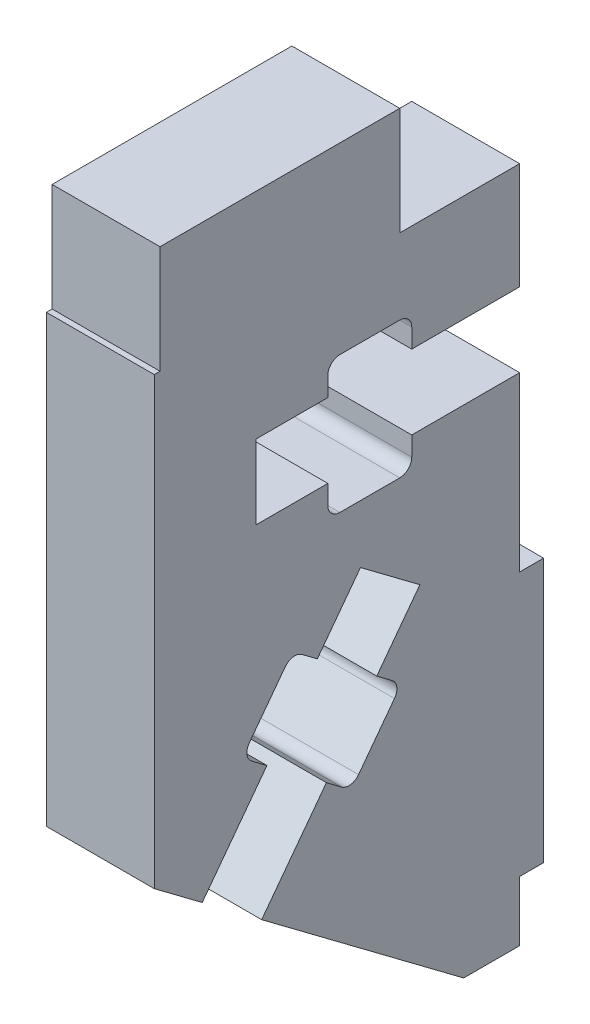
SolidWorks part; units mm, degrees
ref_plane "Front Plane" through (0, 0, 0) normal (0, 0, 1) x (1, 0, 0)
ref_plane "Top Plane" through (0, 0, 0) normal (0, 1, 0) x (1, 0, 0)
ref_plane "Right Plane" through (0, 0, 0) normal (1, 0, 0) x (0, 0, -1)
sketch "Sketch1" plane through (0, 0, 0) normal (1, 0, 0) x (0, 0, -1)
  line L0 (0, 0) -> (0, -30)
  line L1 (0, -30) -> (-40, 0)
  line L2 (-40, 0) -> (0, 0)
  dimension "D1" = 40
  dimension "D2" = 30
extrude "Boss-Extrude1" add sketch "Sketch1" along normal blind 4.5
sketch "Sketch2" plane through (4.5, 0, 0) normal (1, 0, 0) x (0, 0, -1)
  line L0 (0, -25.75) -> (1, -25.75)
  line L1 (0, -30) -> (0, 0) construction
  line L2 (1, -25.75) -> (1, -14.75)
  line L3 (1, -14.75) -> (0, -14.75)
  line L4 (0, -14.75) -> (0, -25.75)
  line L5 (1, -20.25) -> (0, -20.25) construction
  line L6 (0, -14.75) -> (4.5, -14.75) construction
  line L7 (0, -25.75) -> (4.5, -25.75) construction
  dimension "D1" = 0
  dimension "D2" = 1
  dimension "D3" = 0
extrude "Boss-Extrude2" add sketch "Sketch2" against normal through all
sketch "Sketch3" plane through (4.5, 0, 0) normal (1, 0, 0) x (0, 0, -1)
  line L0 (0, -6) -> (-11, -6) construction
  line L1 (0, -14.75) -> (0, 0) construction
  line L2 (-11, -7.55) -> (-11, -4.45) construction
  line L3 (-11, -4.45) -> (0, -4.45) construction
  line L4 (0, -4.45) -> (-4.5, -4.45)
  line L5 (-4.5, -4.45) -> (-4.5, -3.65)
  line L6 (-5, -3.15) -> (-7.5, -3.15)
  line L7 (-8, -3.65) -> (-8, -4.45)
  line L8 (-8, -4.45) -> (-11, -4.45)
  line L9 (-11, -4.45) -> (-11, -7.55)
  line L10 (0, -4.45) -> (0, -7.55)
  line L12 (-11, -7.55) -> (0, -7.55) construction
  line L13 (-8, -7.55) -> (-11, -7.55)
  line L14 (-8, -8.35) -> (-8, -7.55)
  line L15 (-5, -8.85) -> (-7.5, -8.85)
  line L16 (-4.5, -7.55) -> (-4.5, -8.35)
  line L17 (0, -7.55) -> (-4.5, -7.55)
  arc A0 (-4.5, -3.65) -> (-5, -3.15) centre (-5, -3.65) ccw
  arc A1 (-7.5, -3.15) -> (-8, -3.65) centre (-7.5, -3.65) ccw
  arc A2 (-7.5, -8.85) -> (-8, -8.35) centre (-7.5, -8.35) cw
  arc A3 (-4.5, -8.35) -> (-5, -8.85) centre (-5, -8.35) cw
  point P15 (-4.5, -3.15)
  point P18 (-8, -3.15)
  point P29 (-8, -8.85)
  point P30 (-4.5, -8.85)
  dimension "D7" = 0.5
  dimension "D1" = 11
  dimension "D2" = 1.55
  dimension "D3" = 3.5
  dimension "D4" = 2.85
  dimension "D5" = 8
  dimension "D6" = 6
extrude "Cut-Extrude1" cut sketch "Sketch3" against normal through all
sketch "Sketch4" plane through (4.5, 0, 0) normal (1, 0, 0) x (0, 0, -1)
  line L0 (-13.24, -20.07) -> (-6.64, -11.27) construction
  line L1 (-40, 0) -> (0, -30) construction
  line L2 (-6.64, -11.27) -> (-4.16, -13.13) construction
  line L3 (-5.4, -12.2) -> (-12, -21) construction
  line L4 (-10.76, -21.93) -> (-13.24, -20.07)
  line L5 (-13.24, -20.07) -> (-10.54, -16.47)
  line L6 (-10.54, -16.47) -> (-11.18, -15.99)
  line L7 (-11.28, -15.29) -> (-9.78, -13.29)
  line L8 (-9.08, -13.19) -> (-8.44, -13.67)
  line L9 (-8.44, -13.67) -> (-6.64, -11.27)
  line L10 (-6.64, -11.27) -> (-4.16, -13.13)
  line L11 (0, 0) -> (-40, 0) construction
  line L12 (-10.76, -21.93) -> (-4.16, -13.13) construction
  line L13 (-5.96, -15.53) -> (-4.16, -13.13)
  line L14 (-5.32, -16.01) -> (-5.96, -15.53)
  line L15 (-6.72, -18.71) -> (-5.22, -16.71)
  line L16 (-8.06, -18.33) -> (-7.42, -18.81)
  line L17 (-10.76, -21.93) -> (-8.06, -18.33)
  arc A0 (-11.18, -15.99) -> (-11.28, -15.29) centre (-10.88, -15.59) cw
  arc A1 (-9.78, -13.29) -> (-9.08, -13.19) centre (-9.38, -13.59) cw
  arc A2 (-5.22, -16.71) -> (-5.32, -16.01) centre (-5.62, -16.41) ccw
  arc A3 (-7.42, -18.81) -> (-6.72, -18.71) centre (-7.12, -18.41) ccw
  point P14 (-11.58, -15.69)
  point P17 (-9.48, -12.89)
  point P28 (-4.92, -16.31)
  point P29 (-7.02, -19.11)
  dimension "D7" = 0.5
  dimension "D1" = 11
  dimension "D2" = 1.55
  dimension "D3" = 3.5
  dimension "D4" = 2.85
  dimension "D5" = 8
  dimension "D6" = 21
extrude "Cut-Extrude2" cut sketch "Sketch4" against normal through all
sketch "Sketch5" plane through (4.5, 0, 0) normal (1, 0, 0) x (0, 0, -1)
  line L0 (-15.24, -18.57) -> (-15.24, 0)
  line L1 (-40, 0) -> (-13.24, -20.07) construction
  line L2 (0, 0) -> (-40, 0) construction
  line L3 (-15.24, 0) -> (-40, 0)
  line L4 (-40, 0) -> (-15.24, -18.57)
  dimension "D1" = 2
extrude "Cut-Extrude3" cut sketch "Sketch5" against normal through all
sketch "Sketch6" plane through (0, 0, 11) normal (0, 0, -1) x (-1, 0, 0)
  line L0 (-2.25, -4.45) -> (-2.25, -7.55) construction
  line L1 (0, -4.45) -> (-4.5, -4.45) construction
  line L2 (0, -7.55) -> (-4.5, -7.55) construction
  circle A0 centre (-2.25, -6) radius 1.5
  dimension "D1" = 3
sketch "Sketch7" plane through (0, -10.4, 7.8) normal (0, -0.8, 0.6) x (1, 0, 0)
  line L0 (2.25, -1.45) -> (2.25, -4.55) construction
  line L1 (0, -1.45) -> (4.5, -1.45) construction
  line L2 (0, -4.55) -> (4.5, -4.55) construction
  circle A0 centre (2.25, -3) radius 1.55
sketch "Sketch8" plane through (4.5, 0, 0) normal (1, 0, 0) x (0, 0, -1)
  line L0 (-10, 4.5) -> (-10, 0) construction
  line L1 (-15, 0) -> (-5, 0)
  line L2 (-15, 0) -> (-15, 4.5)
  line L3 (-15, 4.5) -> (-5, 4.5)
  line L4 (-5, 0) -> (-5, 4.5)
  line L5 (0, 0) -> (-15.24, 0) construction
  dimension "D1" = 10
  dimension "D2" = 4.5
  dimension "D3" = 10
extrude "Boss-Extrude3" add sketch "Sketch8" against normal through all
sketch "Sketch10" plane through (4.5, 0, 0) normal (1, 0, 0) x (0, 0, -1)
  line L0 (0, -28.25) -> (-2.3333, -28.25)
  line L1 (0, -30) -> (0, -25.75) construction
  line L2 (-10.76, -21.93) -> (0, -30) construction
  line L3 (-2.3333, -28.25) -> (0, -30)
  line L4 (0, -30) -> (0, -28.25)
  dimension "D1" = 0
extrude "Cut-Extrude4" cut sketch "Sketch10" against normal through all contours L0 L3 L4
equation "\"X-ROD-SPACING\"=45"
equation "\"Y-ROD-SPACING\"=75"
equation "\"Z-ROD-SPACING\"=17.5"
equation "\"Y-BED-OFFSET\"=2"
equation "\"Y-BED-ROD-INSET\"=3.5"
equation "\"Y-BED-SCREW-SPACING\"=209"
equation "\"Y-BED-SCREW-CUTOUT-SLOT-HEIGHT\"=2"
equation "\"T-SLOT-NUT-FILLET-RADIUS\"=0.5"
equation "\"T-SLOT-SCREW-SHAFT-RADIUS\"=1.55"
equation "\"T-SLOT-SCREW-SHAFT-CUTOUT-LENGTH\"=11.0"
equation "\"T-SLOT-NUT-DEPTH\"=3.5"
equation "\"T-SLOT-NUT-WIDTH\"=2.85"
equation "\"T-SLOT-NUT-END-DISTANCE\"=8"
equation "\"ACRYLIC-THICKNESS\"=10"
equation "\"ACRYLIC-THICKNESS2\"=4.5"
equation "\"ACRYLIC-TAB-CUTOUT-SIZE\"=\"ACRYLIC-THICKNESS\"+\"ACRYLIC-TAB-TOLERANCE\"*2"
equation "\"ACRYLIC-TAB-TOLERANCE\"=-.05"
equation "\"ACRYLIC-TAB-WIDTH\"=\"ACRYLIC-THICKNESS\""
equation "\"ACRYLIC-M3-HOLE\"=2.9"
equation "\"SMOOTHROD-CAP-SCREW-DISTANCE\"=20"
equation "\"FRAME-WIDTH-INNER\"=370"
equation "\"NEMA17-HOLE-SPACING\"=31"
equation "\"NEMA17-CENTRAL-CUTOUT\"=22.5"
equation "\"Z-BRACKET-REACH\"=55"
equation "\"Z-ROD-INSET\"=16"
equation "\"TOP-BRACKET-SPACING\"=40"
equation "\"SMOOTHROD-X-LENGTH\"=350"
equation "\"SMOOTHROD-Y-LENGTH\"=350"
equation "\"SMOOTHROD-Z-LENGTH\"=350"
equation "\"SMOOTHROD-TIGHTENING-HEADROOM\"=.25"
equation "\"LEADSCREW-Z-LENGTH\"=300"
equation "\"SCREW-LENGTH-FRAME\"=\"ACRYLIC-THICKNESS\" + 10"
equation "\"SCREW-LENGTH-MOTOR\"=\"ACRYLIC-THICKNESS\" + 5"
equation "\"SCREW-LENGTH-EXTRUDER\"=28"
equation "\"SCREW-HEAD-RADIUS\"=6"
equation "\"PRINTED-M3-HOLE\"=3.5"
equation "\"PRINTED-X-SMOOTHROD-DIAMETER\"=9.4"
equation "\"PRINTED-X-SMOOTHROD-CUTOUT\"=10"
equation "\"PRINTED-X-BASE-HEIGHT\"=10"
equation "\"PRINTED-LM8UU-CUTOUT-SIZE\"=15.5"
equation "\"PRINTED-LM8UU-CUTOUT-LENGTH\"=24.5"
equation "\"PRINTED-X-IDLER-HEIGHT\"=16"
equation "\"PRINTED-M3-NUT-AF\"=6.25"
equation "\"PSU-MOUNTING-WIDTH\"=95"
equation "\"PSU-MOUNTING-HEIGHT\"=177"
equation "\"Y-BELT-TO-ROD-DISTANCE\"=20"
equation "\"SPOOL-HOLDER-ROD-SPACING\"=150"
equation "\"ACRYLIC-X-CARRIAGE-WIDTH\"=55"
equation "\"ACRYLIC-X-CARRIAGE-HEIGHT\"=75"
equation "\"ACRYLIC-X-CARRIAGE-LM8UU-CUTOUT-WIDTH\"=24.25"
equation "\"ACRYLIC-X-CARRIAGE-LM8UU-CUTOUT-HEIGHT\"=11.0"
equation "\"ACRYLIC-X-CARRIAGE-SCREW-SPACING-X\"=15"
equation "\"ACRYLIC-X-CARRIAGE-SCREW-SPACING-Y\"=33"
equation "\"ACRYLIC-X-CARRIAGE-CENTER-TAB-SPACING\"=14"
equation "\"ACRYLIC-X-CARRIAGE-EXTRUDER-OFFSET\"=26"
equation "\"ACRYLIC-X-CARRIAGE-EXTRUDER-ANGLE\"=90"
equation "\"ACRYLIC-X-CARRIAGE-EXTRUDER-SHELF-DEPTH\"=\"ACRYLIC-X-CARRIAGE-EXTRUDER-OFFSET\" + 28"
equation "\"ACRYLIC-X-CARRIAGE-EXTRUDER-BRACE-SPACING\"=23"
equation "\"ACRYLIC-X-CARRIAGE-EXTRUDER-BRACE-TAB-OFFSET\"=20"
equation "\"ACRYLIC-X-CARRIAGE-EXTRUDER-BRACE-HEIGHT\"=35"
equation "\"ACRYLIC-X-CARRIAGE-EXTRUDER-BRACE-SCREW-SPACING\"=22"
equation "\"ACRYLIC-X-CARRIAGE-DUAL-WIDTH-MULTIPLIER\"=1.65"
equation "\"ACRYLIC-X-CARRIAGE-DUAL-HOTEND-SPACING\"=42"
equation "\"ACRYLIC-X-CARRIAGE-DUAL-WIDTH\"=75"
equation "\"ACRYLIC-X-CARRIAGE-DUAL-FAN-OFFSET\"=52"
equation "\"ACRYLIC-X-CARRIAGE-DUAL-FAN-HEIGHT\"=20"
equation "\"ACRYLIC-X-CARRIAGE-DUAL-HOTEND-SEPARATION\"=36"
equation "\"ACRYLIC-X-CARRIAGE-DUAL-MOUNT-PLATE-DEPTH\"=75"
equation "\"ACRYLIC-X-CARRIAGE-DUAL-MOUNT-BRACE-WIDTH\"=33"
equation "\"ACRYLIC-X-CARRIAGE-DUAL-MOUNT-SCREW-WIDTH\"=40"
equation "\"BLOWER-FAN-WIDTH\"=15"
equation "\"D1@Boss-Extrude1\"=\"ACRYLIC-THICKNESS2\""
equation "\"D1@Sketch3\"=\"T-SLOT-SCREW-SHAFT-CUTOUT-LENGTH\""
equation "\"D2@Sketch3\"=\"T-SLOT-SCREW-SHAFT-RADIUS\""
equation "\"D3@Sketch3\"=\"T-SLOT-NUT-DEPTH\""
equation "\"D4@Sketch3\"=\"T-SLOT-NUT-WIDTH\""
equation "\"D5@Sketch3\"=\"T-SLOT-NUT-END-DISTANCE\""
equation "\"D7@Sketch3\"=\"T-SLOT-NUT-FILLET-RADIUS\""
equation "\"D1@Sketch4\"=\"T-SLOT-SCREW-SHAFT-CUTOUT-LENGTH\""
equation "\"D2@Sketch4\"=\"T-SLOT-SCREW-SHAFT-RADIUS\""
equation "\"D3@Sketch4\"=\"T-SLOT-NUT-DEPTH\""
equation "\"D4@Sketch4\"=\"T-SLOT-NUT-WIDTH\""
equation "\"D5@Sketch4\"=\"T-SLOT-NUT-END-DISTANCE\""
equation "\"D7@Sketch4\"=\"T-SLOT-NUT-FILLET-RADIUS\""
equation "\"D1@Sketch8\"=\"ACRYLIC-TAB-WIDTH\""
equation "\"D2@Sketch8\"=\"ACRYLIC-THICKNESS2\""
